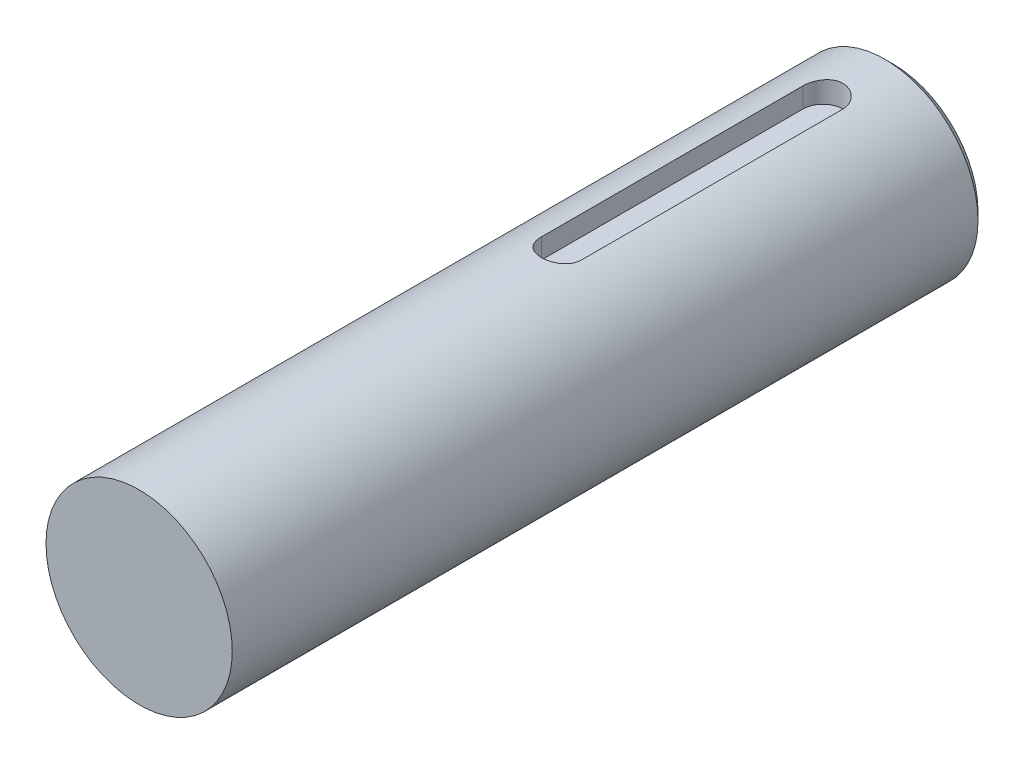
SolidWorks part; units mm, degrees
ref_plane "Płaszczyzna przednia" through (0, 0, 0) normal (0, 0, 1) x (1, 0, 0)
ref_plane "Płaszczyzna górna" through (0, 0, 0) normal (0, 1, 0) x (1, 0, 0)
ref_plane "Płaszczyzna prawa" through (0, 0, 0) normal (1, 0, 0) x (0, 0, -1)
sketch "Szkic1" plane through (0, 0, 0) normal (0, 0, 1) x (1, 0, 0)
  circle A0 centre (0, 0) radius 11.115
  dimension "D1" = 22.23
extrude "Dodanie-wyciągnięcie1" add sketch "Szkic1" along normal blind 90 contours A0
ref_plane "Płaszczyzna1" through (0, 0, 6) normal (0, 0, -1) x (-1, 0, 0)
chamfer "Sfazowanie1" distance 1 angle 45 1 edges at (11.115, 0, 0)
sketch "Szkic2" plane through (0, 0, 6) normal (0, 0, -1) x (-1, 0, 0)
  line L0 (-2.39, 10.855) -> (-2.39, 8.465)
  line L1 (-2.39, 8.465) -> (2.39, 8.465)
  line L2 (2.39, 8.465) -> (2.39, 10.855)
  circle A0 centre (0, 0) radius 11.115 construction
  arc A1 (2.39, 10.855) -> (-2.39, 10.855) centre (0, 0) ccw
  point P5 (0, 8.465)
  dimension "D1" = 4.78
  dimension "D2" = 2.39
extrude "Wytnij-wyciągnięcie1" cut sketch "Szkic2" against normal blind 36
fillet "Zaokrąglenie1" 2 edges at (-2.39, 9.66, 42) (2.39, 9.66, 42) type full round first side face at (-2.39, 9.66, 24) second side face at (2.39, 9.66, 24) middle face at (0, 9.725, 42)
fillet "Zaokrąglenie2" 2 edges at (-2.39, 9.66, 6) (2.39, 9.66, 6) type full round first side face at (-2.39, 9.66, 22.805) second side face at (2.39, 9.66, 22.805) middle face at (0, 9.725, 6)
